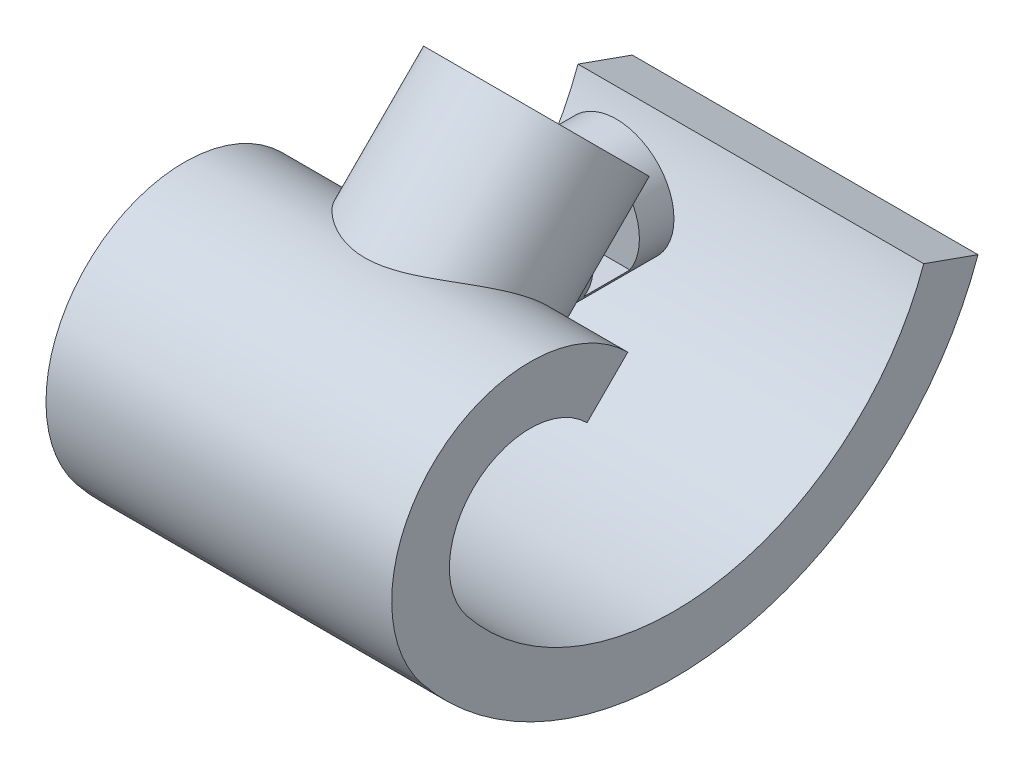
SolidWorks part; units mm, degrees
ref_plane "Спереди" through (0, 0, 0) normal (0, 0, 1) x (1, 0, 0)
ref_plane "Сверху" through (0, 0, 0) normal (0, 1, 0) x (1, 0, 0)
ref_plane "Справа" through (0, 0, 0) normal (1, 0, 0) x (0, 0, -1)
sketch "Sketch1" plane through (0, 0, 0) normal (1, 0, 0) x (0, 0, -1)
  line L0 (-4.0047, 8.4853) -> (-12.49, 0) construction
  line L1 (-12.49, 0) -> (-12.49, 19.5798) construction
  arc A0 (-21.8575, -7.5) -> (26.3823, 0.6205) centre (0, 10) ccw
  arc A1 (-21.8575, -7.5) -> (-4.0047, 8.4853) centre (-12.49, 0) cw
  dimension "D1" = 28
  dimension "D3" = 12
  dimension "D2" = 10
  dimension "D4" = 45
extrude "Extrude-Thin1" add sketch "Sketch1" along normal mid plane 30 thin thin type one direction wall 5
sketch "Sketch2" plane through (0, 0, 0) normal (1, 0, 0) x (0, 0, -1)
  line L0 (-12.49, 0) -> (-4.0047, 8.4853) construction
  line L1 (-4.0047, 8.4853) -> (-12.0252, 16.5058) construction
ref_plane "Plane1" through (0, 2.2403, -2.2403) normal (0, 0.7071, -0.7071) x (1, 0, 0)
sketch "Sketch3" plane through (0, 2.2403, -2.2403) normal (0, 0.7071, -0.7071) x (1, 0, 0)
  line L0 (15, -8.8318) -> (-15, -8.8318) construction
  circle A0 centre (0, -8.8318) radius 4
  circle A1 centre (0, -8.8318) radius 8
  dimension "D1" = 8
  dimension "D2" = 4
extrude "Boss-Extrude1" add sketch "Sketch3" along normal blind 10 and the other way blind 5
sketch "Sketch5" plane through (0, 0, 0) normal (0, 0, 1) x (1, 0, 0)
  circle A0 centre (0, 6.5) radius 5
  point P2 (0, 6.9654)
  dimension "D1" = 10
  dimension "D2" = 6.5
extrude "Boss-Extrude2" add sketch "Sketch5" against normal blind 10
sketch "Sketch6" plane through (0, 0, -10) normal (0, 0, -1) x (-1, 0, 0)
  circle A0 centre (0, 6.5) radius 1.5
  dimension "D1" = 3
extrude "Cut-Extrude2" cut sketch "Sketch6" against normal blind 14
sketch "Sketch4" plane through (0, 9.3114, -9.3114) normal (0, 0.7071, -0.7071) x (1, 0, 0)
  circle A0 centre (0, -8.8318) radius 4
  circle A1 centre (0, -8.8318) radius 4 construction
extrude "Cut-Extrude1" cut sketch "Sketch4" against normal blind 20
ref_plane "Plane2" through (0, 0, -7) normal (0, 0, -1) x (-1, 0, 0)
sketch "Sketch7" plane through (0, 0, -7) normal (0, 0, -1) x (-1, 0, 0)
  line L0 (-1.5877, 9.25) -> (-18.5606, 9.25)
  line L1 (3.1754, 6.5) -> (1.5877, 9.25)
  line L2 (1.5877, 9.25) -> (-1.5877, 9.25)
  line L3 (-1.5877, 9.25) -> (-3.1754, 6.5)
  line L4 (-3.1754, 6.5) -> (-1.5877, 3.75)
  line L5 (-1.5877, 3.75) -> (1.5877, 3.75)
  line L6 (1.5877, 3.75) -> (3.1754, 6.5)
  line L7 (-18.5606, 9.25) -> (-18.5606, 3.75)
  line L8 (-18.5606, 3.75) -> (-1.5877, 3.75)
  circle A0 centre (0, 6.5) radius 2.75 construction
  dimension "D1" = 5.5
extrude "Cut-Extrude3" cut sketch "Sketch7" against normal blind 3 contours L5 L6 L1 L2 L3 L4 | L7 L8 L4 L3 L0 region at (10.4646, 6.5, -7) region at (0, 6.5, -7)
chamfer "Chamfer1" distance 1 angle 45 1 edges at (4.9131, 5.5719, -4)
